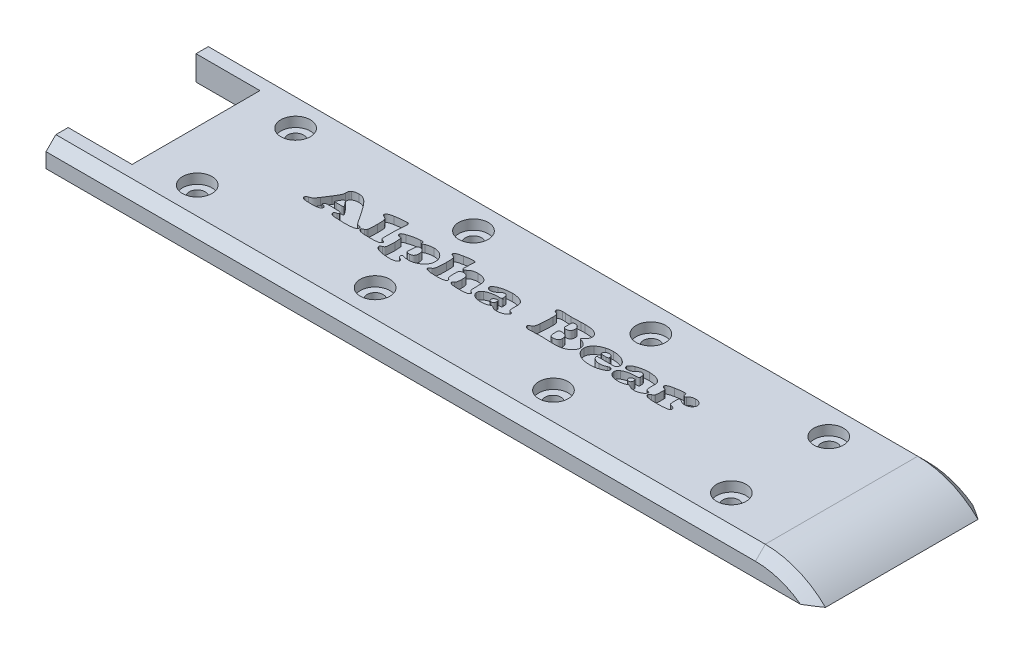
SolidWorks part; units mm, degrees
ref_plane "Front Plane" through (0, 0, 0) normal (0, 0, 1) x (1, 0, 0)
ref_plane "Top Plane" through (0, 0, 0) normal (0, 1, 0) x (1, 0, 0)
ref_plane "Right Plane" through (0, 0, 0) normal (1, 0, 0) x (0, 0, -1)
sketch "Sketch1" plane through (0, 0, 0) normal (0, 0, 1) x (1, 0, 0)
  line L0 (-75, 0) -> (75, 0) construction
  line L4 (-75, 17.5) -> (75, 17.5)
  line L6 (87.2474, 12.5) -> (-87.2474, 12.5)
  arc A2 (-75, 17.5) -> (-87.2474, 12.5) centre (-75, 0) ccw
  arc A3 (87.2474, 12.5) -> (75, 17.5) centre (75, 0) ccw
  point P2 (0, 0)
  point P5 (0, 0)
  dimension "D1" = 17.5
  dimension "D2" = 150
  dimension "D3" = 5
extrude "Boss-Extrude1" add sketch "Sketch1" along normal mid plane 35
sketch "Sketch2" plane through (0, 0, 0) normal (0, 0, 1) x (1, 0, 0)
  line L0 (75, 17.5) -> (-75, 17.5) construction
  line L1 (-87.2474, 12.5) -> (-69.2474, 12.5)
  line L2 (-87.2474, 12.5) -> (-87.2474, 17.5)
  line L3 (-87.2474, 17.5) -> (-69.2474, 17.5)
  line L4 (-69.2474, 12.5) -> (-69.2474, 17.5)
  dimension "D1" = 18
extrude "Cut-Extrude1" cut sketch "Sketch2" against normal mid plane 35
sketch "Sketch3" plane through (0, 12.5, 0) normal (0, -1, 0) x (1, 0, 0)
  line L0 (-69.2474, -17.5) -> (-69.2474, 17.5) construction
  line L1 (-69.2474, -17.5) -> (87.2474, -17.5) construction
  circle A0 centre (-46, -10) radius 1.625
  circle A1 centre (-9.8333, -10) radius 1.625
  circle A2 centre (26.3333, -10) radius 1.625
  circle A3 centre (62.5, -10) radius 1.625
  dimension "D1" = 3.25
  dimension "D2" = 36.1667
  dimension "D3" = 36.1667
  dimension "D4" = 36.1667
  dimension "D5" = 23.2474
  dimension "D6" = 7.5
extrude "Cut-Extrude2" cut sketch "Sketch3" against normal up to surface (5 mm away) up to face at (2.8763, 17.5, 0)
sketch "Sketch4" plane through (0, 17.5, 0) normal (0, 1, 0) x (1, 0, 0)
  circle A0 centre (62.5, 9.9) radius 3
  circle A1 centre (26.3333, 9.9) radius 3
  circle A2 centre (-9.8333, 10) radius 3
  circle A3 centre (-46, 10) radius 3
  dimension "D1" = 6
extrude "Cut-Extrude3" cut sketch "Sketch4" against normal blind 2
mirror "Mirror1" about plane through (0, 0, 0) normal (0, 0, 1) of "Cut-Extrude3", "Cut-Extrude2"
chamfer "Chamfer1" distance 2 angle 45 4 edges at (81.6144, 16.2019, 17.5) (2.8763, 17.5, 17.5) (81.6144, 16.2019, -17.5) (2.8763, 17.5, -17.5)
sketch "Sketch5" plane through (0, 17.5, 0) normal (0, 1, 0) x (1, 0, 0)
  line L1 (-69.2474, 13) -> (-56.2474, 13)
  line L2 (-69.2474, 13) -> (-69.2474, -13)
  line L3 (-69.2474, -13) -> (-56.2474, -13)
  line L4 (-56.2474, 13) -> (-56.2474, -13)
  line L6 (-69.2474, 15.5) -> (-69.2474, -15.5) construction
  line L7 (-69.2474, 17.5) -> (75, 17.5) construction
  point P4 (-56.2474, 0)
  dimension "D1" = 4.5
  dimension "D2" = 13
extrude "Cut-Extrude4" cut sketch "Sketch5" against normal up to surface (5 mm away) up to face at (-44.375, 12.5, 10)
sketch "Sketch6" plane through (0, 17.5, 0) normal (0, 1, 0) x (1, 0, 0)
  line L0 (-56.2474, -1.9184) -> (75, -1.9184) construction
  line L1 (-56.2474, -13) -> (-56.2474, 13) construction
  line L2 (75, -15.5) -> (75, 15.5) construction
  text T0 "Alpha Bear" font "Cooper Black" height in points 28
extrude "Cut-Extrude5" cut sketch "Sketch6" against normal blind 1.5
